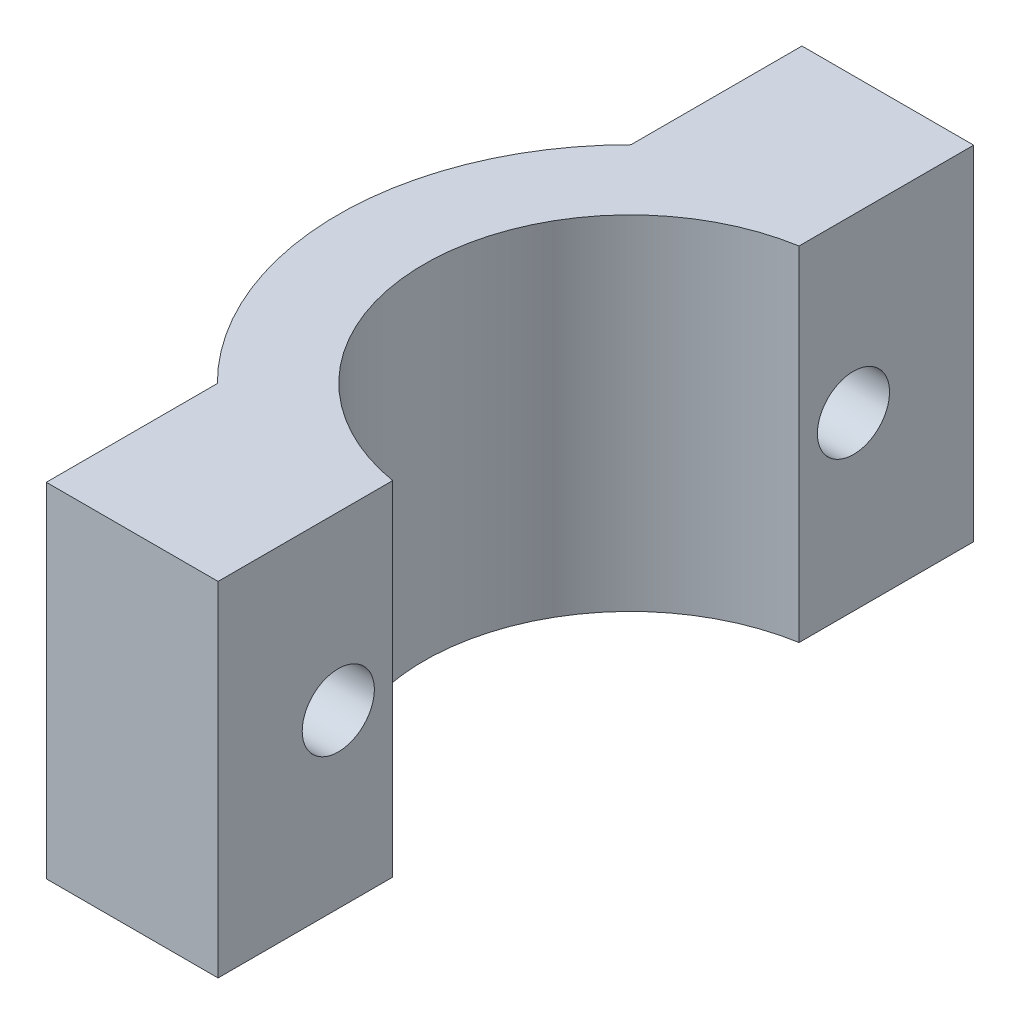
SolidWorks part; units mm, degrees
ref_plane "Front Plane" through (0, 0, 0) normal (0, 0, 1) x (1, 0, 0)
ref_plane "Top Plane" through (0, 0, 0) normal (0, 1, 0) x (1, 0, 0)
ref_plane "Right Plane" through (0, 0, 0) normal (1, 0, 0) x (0, 0, -1)
sketch "Sketch1" plane through (0, 0, 0) normal (0, 1, 0) x (1, 0, 0)
  line L0 (0, 0) -> (-1, 0) construction
  line L5 (-6, 11) -> (-1, 11)
  line L6 (-6, 11) -> (-6, -11)
  line L7 (-6, -11) -> (-1, -11)
  line L8 (-1, 11) -> (-1, -11)
  line L9 (0, 6) -> (-6, 6) construction
  line L10 (0, 6) -> (0, 0) construction
  circle A0 centre (0, 0) radius 6
  circle A1 centre (0, 0) radius 8.5
  dimension "D1" = 12
  dimension "D2" = 17
  dimension "D3" = 5
  dimension "D4" = 5
  dimension "D5" = 1
extrude "Boss-Extrude1" add sketch "Sketch1" against normal blind 10 contours L6 A1 | L8 A1 L6 A0 | L6 A1 L8 A0 | A1 L6 L7 L8 | A1 L8 L5 L6 region at (-3.7864, 0, -9.2184) region at (-3.7653, 0, -5.8131) region at (-7.0138, 0, 0) region at (-3.7653, 0, 5.8131) region at (-3.7864, 0, 9.2184)
sketch "Sketch2" plane through (0, 0, 0) normal (1, 0, 0) x (0, 0, -1)
  line L0 (-5.9161, 0) -> (-11, 0) construction
  line L5 (11, 0) -> (5.9161, 0) construction
  circle A2 centre (-7.5, -5) radius 1.05
  circle A3 centre (7.5, -5) radius 1.05
  circle A4 centre (-7.5, -5) radius 1.75
  circle A5 centre (7.5, -5) radius 1.75
  dimension "D1" = 2.1
  dimension "D6" = 3.5
  dimension "D2" = 5
  dimension "D3" = 7.5
  dimension "D4" = 5
  dimension "D5" = 7.5
extrude "Cut-Extrude1" cut sketch "Sketch2" against normal through all both and the other way through all contours A2 | A3 region at (0, -5, 7.5) region at (0, -5, -7.5)
extrude "Cut-Extrude2" cut sketch "Sketch2<3>" along normal blind 1 and the other way blind 10 from surface contours A4 A2 | A5 A3 region at (0, -5, 9.2005) region at (0, -5, -5.7995) starting at face at (-6, -5, 8.55)
sketch "Sketch2<3>" plane through (0, 0, 0) normal (1, 0, 0) x (0, 0, -1) same geometry as "Sketch2"
